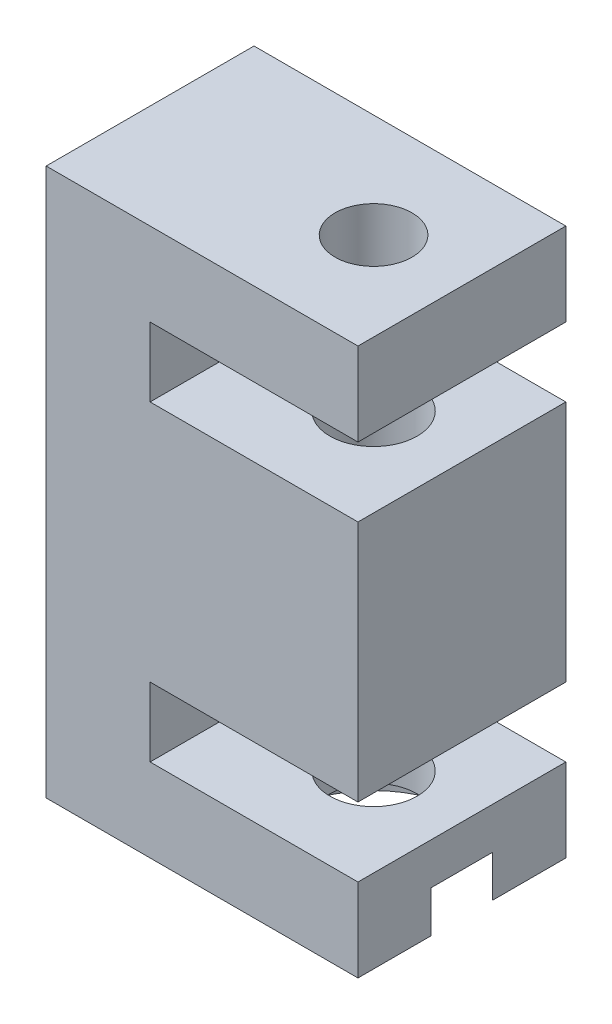
SolidWorks part; units mm, degrees
ref_plane "Front Plane" through (0, 0, 0) normal (0, 0, 1) x (1, 0, 0)
ref_plane "Top Plane" through (0, 0, 0) normal (0, 1, 0) x (1, 0, 0)
ref_plane "Right Plane" through (0, 0, 0) normal (1, 0, 0) x (0, 0, -1)
sketch "Sketch1" plane through (0, 0, 0) normal (0, 0, 1) x (1, 0, 0)
  line L0 (0, 0) -> (0, 4)
  line L1 (0, 4) -> (-15, 4)
  line L2 (-15, 4) -> (-15, -22.33)
  line L3 (-15, -22.33) -> (0, -22.33)
  line L4 (0, -22.33) -> (0, -18.33)
  line L5 (0, -18.33) -> (-10, -18.33)
  line L6 (-10, -18.33) -> (-10, -15)
  line L7 (-10, -15) -> (0, -15)
  line L8 (0, -15) -> (0, -3.33)
  line L9 (0, -3.33) -> (-10, -3.33)
  line L10 (-10, -3.33) -> (-10, 0)
  line L11 (-10, 0) -> (0, 0)
  line L12 (-10, -1.665) -> (1.9622, -1.665) construction
  line L13 (-10, -16.665) -> (1.9586, -16.665) construction
  dimension "D1" = 15
  dimension "D2" = 3.33
  dimension "D3" = 4
  dimension "D4" = 10
  dimension "D5" = 5
extrude "Boss-Extrude1" add sketch "Sketch1" along normal blind 10
sketch "Sketch2" plane through (-15, 0, 0) normal (-1, 0, 0) x (0, 0, 1)
  line L0 (10, 4) -> (10, -22.33) construction
  line L1 (0, -9.165) -> (5, -14.165)
  line L2 (0, -9.165) -> (5, -4.165)
  line L3 (5, -4.165) -> (10, -9.165)
  line L4 (5, -14.165) -> (10, -9.165)
  line L5 (0, -9.165) -> (10, -9.165) construction
  line L6 (5, -4.165) -> (5, -14.165) construction
  line L7 (0, 4) -> (0, -22.33) construction
  line L8 (10, 4) -> (0, -22.33) construction
  point P0 (5, -9.165)
  point P5 (0, 0)
  point P8 (5, -3.926)
  dimension "D1" = 45
sketch "Sketch3" plane through (0, 4, 0) normal (0, 1, 0) x (1, 0, 0)
  line L0 (0, 0) -> (-8.5, -10) construction
  line L1 (0, -10) -> (-15, -10) construction
  line L2 (-10, 0) -> (-10, -10) construction
  line L3 (-10, -10) -> (-10, 0) construction
  line L4 (0, 0) -> (-15, 0) construction
  circle A0 centre (-4.25, -5) radius 1.85
  point P11 (-7.6848, -10)
  point P12 (-7.6848, 0)
  dimension "D1" = 3.7
  dimension "D2" = 1.5
extrude "Cut-Extrude1" cut sketch "Sketch3" against normal up to surface (4 mm away) up to face at (-5, 0, 5)
sketch "Sketch5" plane through (0, -3.33, 0) normal (0, 1, 0) x (1, 0, 0)
  circle A0 centre (-4.25, -5) radius 2.1
  dimension "D1" = 4.2
extrude "Cut-Extrude2" cut sketch "Sketch5" against normal up to surface (19 mm away) up to face at (-7.5, -22.33, 5)
sketch "Sketch6" plane through (0, -22.33, 0) normal (0, -1, 0) x (1, 0, 0)
  circle A0 centre (-4.25, 5) radius 4.5
  dimension "D1" = 9
extrude "Cut-Extrude3" cut sketch "Sketch6" against normal blind 2
ref_plane "Plane1" through (0, 0, 5) normal (0, 0, 1) x (1, 0, 0)
sketch "Sketch7" plane through (0, 0, 5) normal (0, 0, 1) x (1, 0, 0)
  line L0 (-15, 4) -> (-15, -22.33) construction
  circle A0 centre (-15, 4.5832) radius 13.7482
  point P5 (-15, 4.5832)
